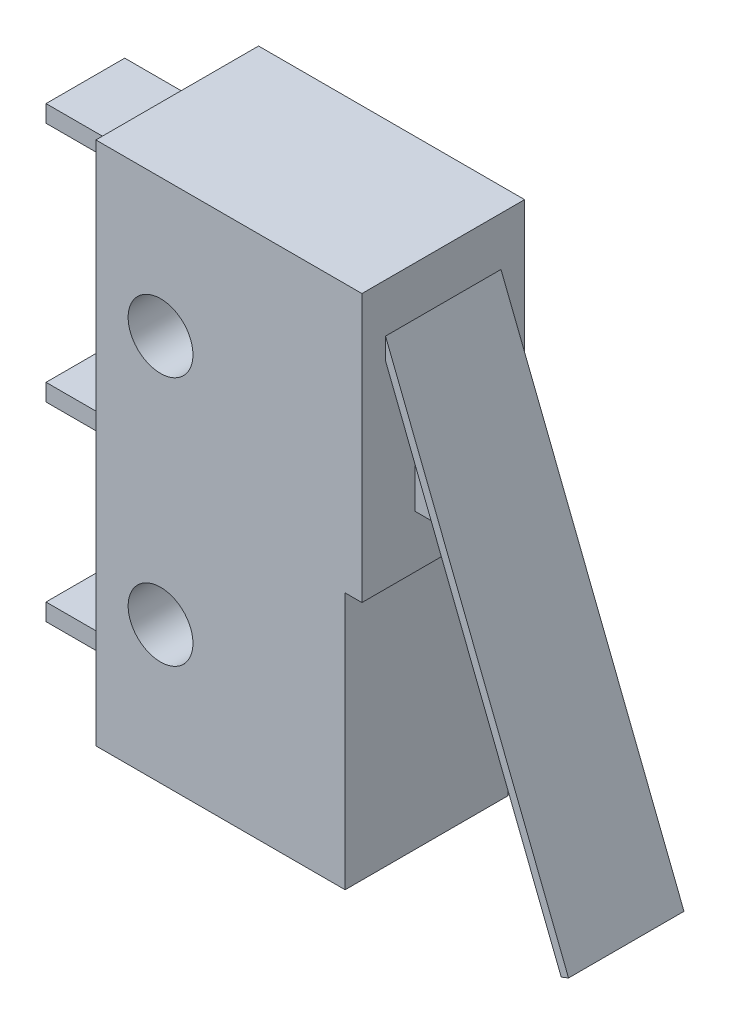
SolidWorks part; units mm, degrees
ref_plane "Front Plane" through (0, 0, 0) normal (0, 0, 1) x (1, 0, 0)
ref_plane "Top Plane" through (0, 0, 0) normal (0, 1, 0) x (1, 0, 0)
ref_plane "Right Plane" through (0, 0, 0) normal (1, 0, 0) x (0, 0, -1)
sketch "Sketch1" plane through (0, 0, 0) normal (0, 0, 1) x (1, 0, 0)
  line L0 (-2.5165, -0.377) -> (-3.1565, -0.377)
  line L1 (-12.6565, 9.823) -> (-2.5165, 9.823)
  line L2 (-12.6565, 9.823) -> (-12.6565, -10.177)
  line L3 (-12.6565, -10.177) -> (-3.1565, -10.177)
  line L4 (-2.5165, 9.823) -> (-2.5165, -0.377)
  line L5 (-3.1565, -0.377) -> (-3.1565, -10.177)
  dimension "D1" = 10.14
  dimension "D2" = 9.5
  dimension "D3" = 10.2
  dimension "D4" = 20
extrude "Boss-Extrude1" add sketch "Sketch1" along normal blind 6.2
sketch "Sketch2" plane through (-12.6565, 0, 0) normal (-1, 0, 0) x (0, 0, 1)
  line L0 (0, 9.823) -> (0, -10.177) construction
  line L1 (1.6, 8.473) -> (4.6, 8.473)
  line L2 (1.6, 8.473) -> (1.6, 7.823)
  line L3 (1.6, 7.823) -> (4.6, 7.823)
  line L4 (4.6, 8.473) -> (4.6, 7.823)
  line L5 (1.6, -0.727) -> (4.6, -0.727)
  line L6 (1.6, -0.727) -> (1.6, -1.377)
  line L7 (1.6, -1.377) -> (4.6, -1.377)
  line L8 (4.6, -0.727) -> (4.6, -1.377)
  line L9 (1.6, -7.977) -> (4.6, -7.977)
  line L10 (1.6, -7.977) -> (1.6, -8.627)
  line L11 (1.6, -8.627) -> (4.6, -8.627)
  line L12 (4.6, -7.977) -> (4.6, -8.627)
  line L13 (6.2, 9.823) -> (0, 9.823) construction
  line L14 (6.2, -10.177) -> (0, -10.177) construction
  dimension "D1" = 0.65
  dimension "D2" = 3
  dimension "D3" = 1.6
  dimension "D4" = 2
  dimension "D5" = 2.2
  dimension "D6" = 11.2
extrude "Boss-Extrude2" add sketch "Sketch2" along normal blind 3.5 separate body
sketch "Sketch3" plane through (0, 0, 6.2) normal (0, 0, 1) x (1, 0, 0)
  line L0 (-2.5165, 9.823) -> (-12.6565, 9.823) construction
  line L1 (-12.6565, -10.177) -> (-3.1565, -10.177) construction
  line L2 (-3.1565, -10.177) -> (-3.1565, -0.377) construction
  circle A0 centre (-10.1915, 4.583) radius 1.235
  circle A1 centre (-10.1915, -4.942) radius 1.235
  dimension "D1" = 2.47
  dimension "D2" = 2.47
  dimension "D5" = 7.035
  dimension "D3" = 5.24
  dimension "D4" = 5.235
extrude "Cut-Extrude1" cut sketch "Sketch3" against normal up to next (6.2 mm away)
sketch "Sketch4" plane through (-2.5165, 0, 0) normal (1, 0, 0) x (0, 0, -1)
  line L1 (-4.175, 3.123) -> (-1.925, 3.123)
  line L2 (-4.175, 3.123) -> (-4.175, 1.623)
  line L3 (-4.175, 1.623) -> (-1.925, 1.623)
  line L4 (-1.925, 3.123) -> (-1.925, 1.623)
  line L5 (-6.2, -0.377) -> (-6.2, 9.823) construction
  line L6 (-6.2, 9.823) -> (0, 9.823) construction
  dimension "D1" = 2.25
  dimension "D2" = 1.5
  dimension "D3" = 2.025
  dimension "D4" = 8.2
extrude "Boss-Extrude4" add sketch "Sketch4" along normal blind 2
ref_plane "Plane2" through (0, 0, 3.1) normal (0, 0, 1) x (1, 0, 0)
fillet "Fillet1" radius 1 2 edges at (-0.5165, 3.123, 3.05) (-0.5165, 1.623, 3.05)
sketch "Sketch5" plane through (0, 0, 3.1) normal (0, 0, 1) x (1, 0, 0)
  line L0 (-2.5165, 7.9685) -> (4.4573, -9.7313)
  line L1 (-2.5165, -0.377) -> (-2.5165, 9.823) construction
  line L2 (4.4573, -9.7313) -> (4.1782, -9.8413)
  line L3 (4.1782, -9.8413) -> (-2.7956, 7.8585)
  line L4 (-2.5165, 7.9685) -> (-2.7956, 7.8585)
  dimension "D1" = 0.3
extrude "Boss-Extrude5" add sketch "Sketch5" along normal blind 2.2 and the other way blind 2.2 separate body
